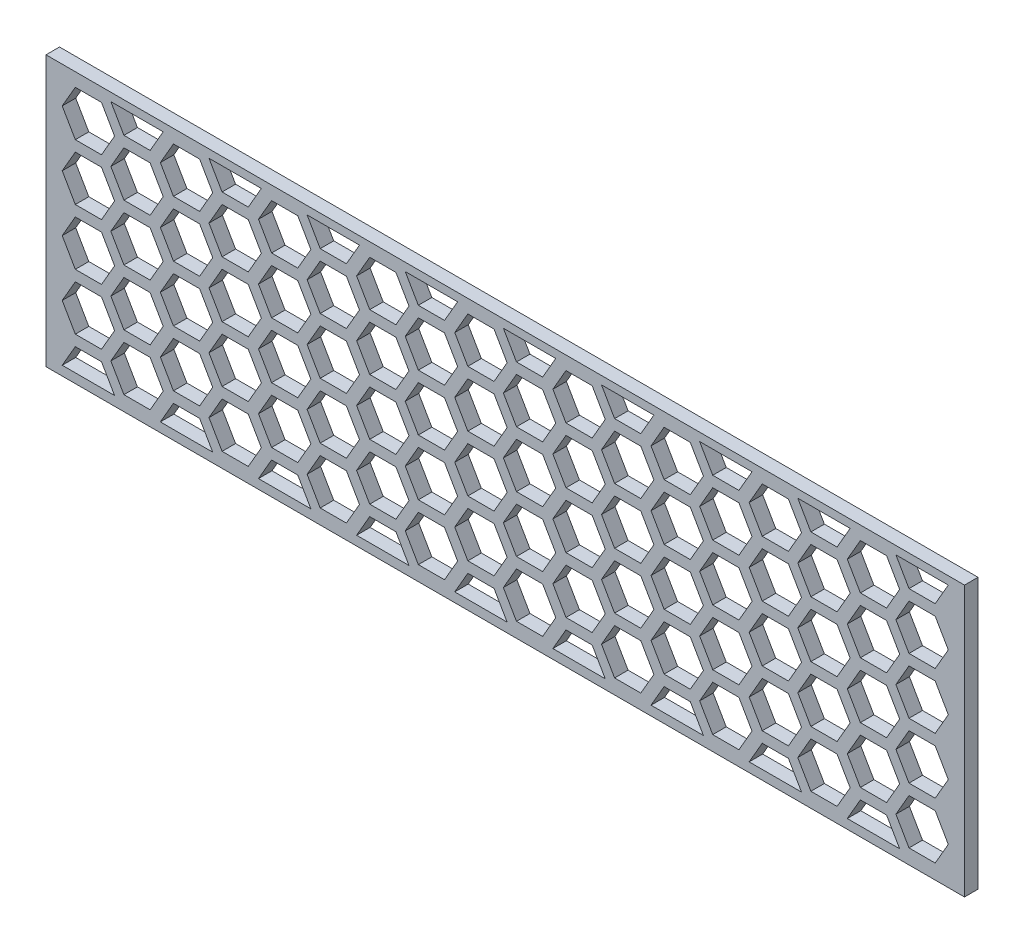
SolidWorks part; units mm, degrees
ref_plane "Plano frontal" through (0, 0, 0) normal (0, 0, 1) x (1, 0, 0)
ref_plane "Plano superior" through (0, 0, 0) normal (0, 1, 0) x (1, 0, 0)
ref_plane "Plano direito" through (0, 0, 0) normal (1, 0, 0) x (0, 0, -1)
sketch "Esboço1" plane through (0, 0, 0) normal (0, 0, 1) x (1, 0, 0)
  line L1 (-85, 25) -> (85, 25)
  line L2 (-85, 25) -> (-85, -25)
  line L3 (-85, -25) -> (85, -25)
  line L4 (85, 25) -> (85, -25)
  line L5 (-85, 25) -> (85, -25) construction
  line L6 (-85, -25) -> (85, 25) construction
  point P0 (0, 0)
  dimension "D1" = 170
  dimension "D2" = 50
extrude "Ressalto-extrusão1" add sketch "Esboço1" along normal blind 2.5
sketch "Esboço3" plane through (0, 0, 0) normal (0, 0, -1) x (-1, 0, 0)
  line L0 (-72.3051, 23.5) -> (-70.5763, 22.5019) construction
  line L4 (-82, 23.5) -> (-79.5763, 19.302)
  line L5 (-79.5763, 19.302) -> (-74.7288, 19.302)
  line L6 (-74.7288, 19.302) -> (-72.3051, 23.5)
  line L7 (-63.3051, 18.3038) -> (-65.7288, 22.5019)
  line L8 (-65.7288, 22.5019) -> (-70.5763, 22.5019)
  line L9 (-70.5763, 22.5019) -> (-73, 18.3038)
  line L10 (-73, 18.3038) -> (-70.5763, 14.1058)
  line L11 (-70.5763, 14.1058) -> (-65.7288, 14.1058)
  line L12 (-65.7288, 14.1058) -> (-63.3051, 18.3038)
  line L13 (-85, 25) -> (85, 25) construction
  line L14 (63.3051, 23.5) -> (73, 23.5)
  line L15 (-73, 18.3038) -> (-80.4849, 18.3038) construction
  line L19 (-63.8369, 23.5) -> (-61.4131, 19.302)
  line L20 (-61.4131, 19.302) -> (-56.5657, 19.302)
  line L21 (-56.5657, 19.302) -> (-54.142, 23.5)
  line L22 (-45.142, 18.3038) -> (-47.5657, 22.5019)
  line L23 (-47.5657, 22.5019) -> (-52.4131, 22.5019)
  line L24 (-52.4131, 22.5019) -> (-54.8369, 18.3038)
  line L25 (-54.8369, 18.3038) -> (-52.4131, 14.1058)
  line L26 (-52.4131, 14.1058) -> (-47.5657, 14.1058)
  line L27 (-47.5657, 14.1058) -> (-45.142, 18.3038)
  line L31 (-45.6737, 23.5) -> (-43.25, 19.302)
  line L32 (-43.25, 19.302) -> (-38.4026, 19.302)
  line L33 (-38.4026, 19.302) -> (-35.9788, 23.5)
  line L34 (-26.9788, 18.3038) -> (-29.4026, 22.5019)
  line L35 (-29.4026, 22.5019) -> (-34.25, 22.5019)
  line L36 (-34.25, 22.5019) -> (-36.6737, 18.3038)
  line L37 (-36.6737, 18.3038) -> (-34.25, 14.1058)
  line L38 (-34.25, 14.1058) -> (-29.4026, 14.1058)
  line L39 (-29.4026, 14.1058) -> (-26.9788, 18.3038)
  line L43 (-27.5106, 23.5) -> (-25.0869, 19.302)
  line L44 (-25.0869, 19.302) -> (-20.2394, 19.302)
  line L45 (-20.2394, 19.302) -> (-17.8157, 23.5)
  line L46 (-8.8157, 18.3038) -> (-11.2394, 22.5019)
  line L47 (-11.2394, 22.5019) -> (-16.0869, 22.5019)
  line L48 (-16.0869, 22.5019) -> (-18.5106, 18.3038)
  line L49 (-18.5106, 18.3038) -> (-16.0869, 14.1058)
  line L50 (-16.0869, 14.1058) -> (-11.2394, 14.1058)
  line L51 (-11.2394, 14.1058) -> (-8.8157, 18.3038)
  line L55 (-9.3474, 23.5) -> (-6.9237, 19.302)
  line L56 (-6.9237, 19.302) -> (-2.0763, 19.302)
  line L57 (-2.0763, 19.302) -> (0.3474, 23.5)
  line L58 (9.3474, 18.3038) -> (6.9237, 22.5019)
  line L59 (6.9237, 22.5019) -> (2.0763, 22.5019)
  line L60 (2.0763, 22.5019) -> (-0.3474, 18.3038)
  line L61 (-0.3474, 18.3038) -> (2.0763, 14.1058)
  line L62 (2.0763, 14.1058) -> (6.9237, 14.1058)
  line L63 (6.9237, 14.1058) -> (9.3474, 18.3038)
  line L67 (8.8157, 23.5) -> (11.2394, 19.302)
  line L68 (11.2394, 19.302) -> (16.0869, 19.302)
  line L69 (16.0869, 19.302) -> (18.5106, 23.5)
  line L70 (27.5106, 18.3038) -> (25.0869, 22.5019)
  line L71 (25.0869, 22.5019) -> (20.2394, 22.5019)
  line L72 (20.2394, 22.5019) -> (17.8157, 18.3038)
  line L73 (17.8157, 18.3038) -> (20.2394, 14.1058)
  line L74 (20.2394, 14.1058) -> (25.0869, 14.1058)
  line L75 (25.0869, 14.1058) -> (27.5106, 18.3038)
  line L79 (26.9788, 23.5) -> (29.4026, 19.302)
  line L80 (29.4026, 19.302) -> (34.25, 19.302)
  line L81 (34.25, 19.302) -> (36.6737, 23.5)
  line L82 (45.6737, 18.3038) -> (43.25, 22.5019)
  line L83 (43.25, 22.5019) -> (38.4026, 22.5019)
  line L84 (38.4026, 22.5019) -> (35.9788, 18.3038)
  line L85 (35.9788, 18.3038) -> (38.4026, 14.1058)
  line L86 (38.4026, 14.1058) -> (43.25, 14.1058)
  line L87 (43.25, 14.1058) -> (45.6737, 18.3038)
  line L91 (45.142, 23.5) -> (47.5657, 19.302)
  line L92 (47.5657, 19.302) -> (52.4131, 19.302)
  line L93 (52.4131, 19.302) -> (54.8369, 23.5)
  line L94 (63.8369, 18.3038) -> (61.4131, 22.5019)
  line L95 (61.4131, 22.5019) -> (56.5657, 22.5019)
  line L96 (56.5657, 22.5019) -> (54.142, 18.3038)
  line L97 (54.142, 18.3038) -> (56.5657, 14.1058)
  line L98 (56.5657, 14.1058) -> (61.4131, 14.1058)
  line L99 (61.4131, 14.1058) -> (63.8369, 18.3038)
  line L103 (63.3051, 23.5) -> (65.7288, 19.302)
  line L104 (65.7288, 19.302) -> (70.5763, 19.302)
  line L105 (70.5763, 19.302) -> (73, 23.5)
  line L106 (82, 18.3038) -> (79.5763, 22.5019)
  line L107 (79.5763, 22.5019) -> (74.7288, 22.5019)
  line L108 (74.7288, 22.5019) -> (72.3051, 18.3038)
  line L109 (72.3051, 18.3038) -> (74.7288, 14.1058)
  line L110 (74.7288, 14.1058) -> (79.5763, 14.1058)
  line L111 (79.5763, 14.1058) -> (82, 18.3038)
  line L112 (-54.142, 13.1077) -> (-56.5657, 17.3057)
  line L113 (-56.5657, 17.3057) -> (-61.4131, 17.3057)
  line L114 (-61.4131, 17.3057) -> (-63.8369, 13.1077)
  line L115 (-63.8369, 13.1077) -> (-61.4131, 8.9097)
  line L116 (-61.4131, 8.9097) -> (-56.5657, 8.9097)
  line L117 (-56.5657, 8.9097) -> (-54.142, 13.1077)
  line L118 (-45.142, 7.9115) -> (-47.5657, 12.1095)
  line L119 (-47.5657, 12.1095) -> (-52.4131, 12.1095)
  line L120 (-52.4131, 12.1095) -> (-54.8369, 7.9115)
  line L121 (-54.8369, 7.9115) -> (-52.4131, 3.7135)
  line L122 (-52.4131, 3.7135) -> (-47.5657, 3.7135)
  line L123 (-47.5657, 3.7135) -> (-45.142, 7.9115)
  line L124 (-35.9788, 13.1077) -> (-38.4026, 17.3057)
  line L125 (-38.4026, 17.3057) -> (-43.25, 17.3057)
  line L126 (-43.25, 17.3057) -> (-45.6737, 13.1077)
  line L127 (-45.6737, 13.1077) -> (-43.25, 8.9097)
  line L128 (-43.25, 8.9097) -> (-38.4026, 8.9097)
  line L129 (-38.4026, 8.9097) -> (-35.9788, 13.1077)
  line L130 (-26.9788, 7.9115) -> (-29.4026, 12.1095)
  line L131 (-29.4026, 12.1095) -> (-34.25, 12.1095)
  line L132 (-34.25, 12.1095) -> (-36.6737, 7.9115)
  line L133 (-36.6737, 7.9115) -> (-34.25, 3.7135)
  line L134 (-34.25, 3.7135) -> (-29.4026, 3.7135)
  line L135 (-29.4026, 3.7135) -> (-26.9788, 7.9115)
  line L136 (-17.8157, 13.1077) -> (-20.2394, 17.3057)
  line L137 (-20.2394, 17.3057) -> (-25.0869, 17.3057)
  line L138 (-25.0869, 17.3057) -> (-27.5106, 13.1077)
  line L139 (-27.5106, 13.1077) -> (-25.0869, 8.9097)
  line L140 (-25.0869, 8.9097) -> (-20.2394, 8.9097)
  line L141 (-20.2394, 8.9097) -> (-17.8157, 13.1077)
  line L142 (-8.8157, 7.9115) -> (-11.2394, 12.1095)
  line L143 (-11.2394, 12.1095) -> (-16.0869, 12.1095)
  line L144 (-16.0869, 12.1095) -> (-18.5106, 7.9115)
  line L145 (-18.5106, 7.9115) -> (-16.0869, 3.7135)
  line L146 (-16.0869, 3.7135) -> (-11.2394, 3.7135)
  line L147 (-11.2394, 3.7135) -> (-8.8157, 7.9115)
  line L148 (0.3474, 13.1077) -> (-2.0763, 17.3057)
  line L149 (-2.0763, 17.3057) -> (-6.9237, 17.3057)
  line L150 (-6.9237, 17.3057) -> (-9.3474, 13.1077)
  line L151 (-9.3474, 13.1077) -> (-6.9237, 8.9097)
  line L152 (-6.9237, 8.9097) -> (-2.0763, 8.9097)
  line L153 (-2.0763, 8.9097) -> (0.3474, 13.1077)
  line L154 (9.3474, 7.9115) -> (6.9237, 12.1095)
  line L155 (6.9237, 12.1095) -> (2.0763, 12.1095)
  line L156 (2.0763, 12.1095) -> (-0.3474, 7.9115)
  line L157 (-0.3474, 7.9115) -> (2.0763, 3.7135)
  line L158 (2.0763, 3.7135) -> (6.9237, 3.7135)
  line L159 (6.9237, 3.7135) -> (9.3474, 7.9115)
  line L160 (18.5106, 13.1077) -> (16.0869, 17.3057)
  line L161 (16.0869, 17.3057) -> (11.2394, 17.3057)
  line L162 (11.2394, 17.3057) -> (8.8157, 13.1077)
  line L163 (8.8157, 13.1077) -> (11.2394, 8.9097)
  line L164 (11.2394, 8.9097) -> (16.0869, 8.9097)
  line L165 (16.0869, 8.9097) -> (18.5106, 13.1077)
  line L166 (27.5106, 7.9115) -> (25.0869, 12.1095)
  line L167 (25.0869, 12.1095) -> (20.2394, 12.1095)
  line L168 (20.2394, 12.1095) -> (17.8157, 7.9115)
  line L169 (17.8157, 7.9115) -> (20.2394, 3.7135)
  line L170 (20.2394, 3.7135) -> (25.0869, 3.7135)
  line L171 (25.0869, 3.7135) -> (27.5106, 7.9115)
  line L172 (36.6737, 13.1077) -> (34.25, 17.3057)
  line L173 (34.25, 17.3057) -> (29.4026, 17.3057)
  line L174 (29.4026, 17.3057) -> (26.9788, 13.1077)
  line L175 (26.9788, 13.1077) -> (29.4026, 8.9097)
  line L176 (29.4026, 8.9097) -> (34.25, 8.9097)
  line L177 (34.25, 8.9097) -> (36.6737, 13.1077)
  line L178 (45.6737, 7.9115) -> (43.25, 12.1095)
  line L179 (43.25, 12.1095) -> (38.4026, 12.1095)
  line L180 (38.4026, 12.1095) -> (35.9788, 7.9115)
  line L181 (35.9788, 7.9115) -> (38.4026, 3.7135)
  line L182 (38.4026, 3.7135) -> (43.25, 3.7135)
  line L183 (43.25, 3.7135) -> (45.6737, 7.9115)
  line L184 (54.8369, 13.1077) -> (52.4131, 17.3057)
  line L185 (52.4131, 17.3057) -> (47.5657, 17.3057)
  line L186 (47.5657, 17.3057) -> (45.142, 13.1077)
  line L187 (45.142, 13.1077) -> (47.5657, 8.9097)
  line L188 (47.5657, 8.9097) -> (52.4131, 8.9097)
  line L189 (52.4131, 8.9097) -> (54.8369, 13.1077)
  line L190 (63.8369, 7.9115) -> (61.4131, 12.1095)
  line L191 (61.4131, 12.1095) -> (56.5657, 12.1095)
  line L192 (56.5657, 12.1095) -> (54.142, 7.9115)
  line L193 (54.142, 7.9115) -> (56.5657, 3.7135)
  line L194 (56.5657, 3.7135) -> (61.4131, 3.7135)
  line L195 (61.4131, 3.7135) -> (63.8369, 7.9115)
  line L196 (73, 13.1077) -> (70.5763, 17.3057)
  line L197 (70.5763, 17.3057) -> (65.7288, 17.3057)
  line L198 (65.7288, 17.3057) -> (63.3051, 13.1077)
  line L199 (63.3051, 13.1077) -> (65.7288, 8.9097)
  line L200 (65.7288, 8.9097) -> (70.5763, 8.9097)
  line L201 (70.5763, 8.9097) -> (73, 13.1077)
  line L202 (82, 7.9115) -> (79.5763, 12.1095)
  line L203 (79.5763, 12.1095) -> (74.7288, 12.1095)
  line L204 (74.7288, 12.1095) -> (72.3051, 7.9115)
  line L205 (72.3051, 7.9115) -> (74.7288, 3.7135)
  line L206 (74.7288, 3.7135) -> (79.5763, 3.7135)
  line L207 (79.5763, 3.7135) -> (82, 7.9115)
  line L208 (-54.142, 2.7154) -> (-56.5657, 6.9134)
  line L209 (-56.5657, 6.9134) -> (-61.4131, 6.9134)
  line L210 (-61.4131, 6.9134) -> (-63.8369, 2.7154)
  line L211 (-63.8369, 2.7154) -> (-61.4131, -1.4826)
  line L212 (-61.4131, -1.4826) -> (-56.5657, -1.4826)
  line L213 (-56.5657, -1.4826) -> (-54.142, 2.7154)
  line L214 (-45.142, -2.4808) -> (-47.5657, 1.7172)
  line L215 (-47.5657, 1.7172) -> (-52.4131, 1.7172)
  line L216 (-52.4131, 1.7172) -> (-54.8369, -2.4808)
  line L217 (-54.8369, -2.4808) -> (-52.4131, -6.6788)
  line L218 (-52.4131, -6.6788) -> (-47.5657, -6.6788)
  line L219 (-47.5657, -6.6788) -> (-45.142, -2.4808)
  line L220 (-35.9788, 2.7154) -> (-38.4026, 6.9134)
  line L221 (-38.4026, 6.9134) -> (-43.25, 6.9134)
  line L222 (-43.25, 6.9134) -> (-45.6737, 2.7154)
  line L223 (-45.6737, 2.7154) -> (-43.25, -1.4826)
  line L224 (-43.25, -1.4826) -> (-38.4026, -1.4826)
  line L225 (-38.4026, -1.4826) -> (-35.9788, 2.7154)
  line L226 (-26.9788, -2.4808) -> (-29.4026, 1.7172)
  line L227 (-29.4026, 1.7172) -> (-34.25, 1.7172)
  line L228 (-34.25, 1.7172) -> (-36.6737, -2.4808)
  line L229 (-36.6737, -2.4808) -> (-34.25, -6.6788)
  line L230 (-34.25, -6.6788) -> (-29.4026, -6.6788)
  line L231 (-29.4026, -6.6788) -> (-26.9788, -2.4808)
  line L232 (-17.8157, 2.7154) -> (-20.2394, 6.9134)
  line L233 (-20.2394, 6.9134) -> (-25.0869, 6.9134)
  line L234 (-25.0869, 6.9134) -> (-27.5106, 2.7154)
  line L235 (-27.5106, 2.7154) -> (-25.0869, -1.4826)
  line L236 (-25.0869, -1.4826) -> (-20.2394, -1.4826)
  line L237 (-20.2394, -1.4826) -> (-17.8157, 2.7154)
  line L238 (-8.8157, -2.4808) -> (-11.2394, 1.7172)
  line L239 (-11.2394, 1.7172) -> (-16.0869, 1.7172)
  line L240 (-16.0869, 1.7172) -> (-18.5106, -2.4808)
  line L241 (-18.5106, -2.4808) -> (-16.0869, -6.6788)
  line L242 (-16.0869, -6.6788) -> (-11.2394, -6.6788)
  line L243 (-11.2394, -6.6788) -> (-8.8157, -2.4808)
  line L244 (0.3474, 2.7154) -> (-2.0763, 6.9134)
  line L245 (-2.0763, 6.9134) -> (-6.9237, 6.9134)
  line L246 (-6.9237, 6.9134) -> (-9.3474, 2.7154)
  line L247 (-9.3474, 2.7154) -> (-6.9237, -1.4826)
  line L248 (-6.9237, -1.4826) -> (-2.0763, -1.4826)
  line L249 (-2.0763, -1.4826) -> (0.3474, 2.7154)
  line L250 (9.3474, -2.4808) -> (6.9237, 1.7172)
  line L251 (6.9237, 1.7172) -> (2.0763, 1.7172)
  line L252 (2.0763, 1.7172) -> (-0.3474, -2.4808)
  line L253 (-0.3474, -2.4808) -> (2.0763, -6.6788)
  line L254 (2.0763, -6.6788) -> (6.9237, -6.6788)
  line L255 (6.9237, -6.6788) -> (9.3474, -2.4808)
  line L256 (18.5106, 2.7154) -> (16.0869, 6.9134)
  line L257 (16.0869, 6.9134) -> (11.2394, 6.9134)
  line L258 (11.2394, 6.9134) -> (8.8157, 2.7154)
  line L259 (8.8157, 2.7154) -> (11.2394, -1.4826)
  line L260 (11.2394, -1.4826) -> (16.0869, -1.4826)
  line L261 (16.0869, -1.4826) -> (18.5106, 2.7154)
  line L262 (27.5106, -2.4808) -> (25.0869, 1.7172)
  line L263 (25.0869, 1.7172) -> (20.2394, 1.7172)
  line L264 (20.2394, 1.7172) -> (17.8157, -2.4808)
  line L265 (17.8157, -2.4808) -> (20.2394, -6.6788)
  line L266 (20.2394, -6.6788) -> (25.0869, -6.6788)
  line L267 (25.0869, -6.6788) -> (27.5106, -2.4808)
  line L268 (36.6737, 2.7154) -> (34.25, 6.9134)
  line L269 (34.25, 6.9134) -> (29.4026, 6.9134)
  line L270 (29.4026, 6.9134) -> (26.9788, 2.7154)
  line L271 (26.9788, 2.7154) -> (29.4026, -1.4826)
  line L272 (29.4026, -1.4826) -> (34.25, -1.4826)
  line L273 (34.25, -1.4826) -> (36.6737, 2.7154)
  line L274 (45.6737, -2.4808) -> (43.25, 1.7172)
  line L275 (43.25, 1.7172) -> (38.4026, 1.7172)
  line L276 (38.4026, 1.7172) -> (35.9788, -2.4808)
  line L277 (35.9788, -2.4808) -> (38.4026, -6.6788)
  line L278 (38.4026, -6.6788) -> (43.25, -6.6788)
  line L279 (43.25, -6.6788) -> (45.6737, -2.4808)
  line L280 (54.8369, 2.7154) -> (52.4131, 6.9134)
  line L281 (52.4131, 6.9134) -> (47.5657, 6.9134)
  line L282 (47.5657, 6.9134) -> (45.142, 2.7154)
  line L283 (45.142, 2.7154) -> (47.5657, -1.4826)
  line L284 (47.5657, -1.4826) -> (52.4131, -1.4826)
  line L285 (52.4131, -1.4826) -> (54.8369, 2.7154)
  line L286 (63.8369, -2.4808) -> (61.4131, 1.7172)
  line L287 (61.4131, 1.7172) -> (56.5657, 1.7172)
  line L288 (56.5657, 1.7172) -> (54.142, -2.4808)
  line L289 (54.142, -2.4808) -> (56.5657, -6.6788)
  line L290 (56.5657, -6.6788) -> (61.4131, -6.6788)
  line L291 (61.4131, -6.6788) -> (63.8369, -2.4808)
  line L292 (73, 2.7154) -> (70.5763, 6.9134)
  line L293 (70.5763, 6.9134) -> (65.7288, 6.9134)
  line L294 (65.7288, 6.9134) -> (63.3051, 2.7154)
  line L295 (63.3051, 2.7154) -> (65.7288, -1.4826)
  line L296 (65.7288, -1.4826) -> (70.5763, -1.4826)
  line L297 (70.5763, -1.4826) -> (73, 2.7154)
  line L298 (82, -2.4808) -> (79.5763, 1.7172)
  line L299 (79.5763, 1.7172) -> (74.7288, 1.7172)
  line L300 (74.7288, 1.7172) -> (72.3051, -2.4808)
  line L301 (72.3051, -2.4808) -> (74.7288, -6.6788)
  line L302 (74.7288, -6.6788) -> (79.5763, -6.6788)
  line L303 (79.5763, -6.6788) -> (82, -2.4808)
  line L304 (-54.142, -7.6769) -> (-56.5657, -3.4789)
  line L305 (-56.5657, -3.4789) -> (-61.4131, -3.4789)
  line L306 (-61.4131, -3.4789) -> (-63.8369, -7.6769)
  line L307 (-63.8369, -7.6769) -> (-61.4131, -11.8749)
  line L308 (-61.4131, -11.8749) -> (-56.5657, -11.8749)
  line L309 (-56.5657, -11.8749) -> (-54.142, -7.6769)
  line L310 (-45.142, -12.8731) -> (-47.5657, -8.6751)
  line L311 (-47.5657, -8.6751) -> (-52.4131, -8.6751)
  line L312 (-52.4131, -8.6751) -> (-54.8369, -12.8731)
  line L313 (-54.8369, -12.8731) -> (-52.4131, -17.0711)
  line L314 (-52.4131, -17.0711) -> (-47.5657, -17.0711)
  line L315 (-47.5657, -17.0711) -> (-45.142, -12.8731)
  line L316 (-35.9788, -7.6769) -> (-38.4026, -3.4789)
  line L317 (-38.4026, -3.4789) -> (-43.25, -3.4789)
  line L318 (-43.25, -3.4789) -> (-45.6737, -7.6769)
  line L319 (-45.6737, -7.6769) -> (-43.25, -11.8749)
  line L320 (-43.25, -11.8749) -> (-38.4026, -11.8749)
  line L321 (-38.4026, -11.8749) -> (-35.9788, -7.6769)
  line L322 (-26.9788, -12.8731) -> (-29.4026, -8.6751)
  line L323 (-29.4026, -8.6751) -> (-34.25, -8.6751)
  line L324 (-34.25, -8.6751) -> (-36.6737, -12.8731)
  line L325 (-36.6737, -12.8731) -> (-34.25, -17.0711)
  line L326 (-34.25, -17.0711) -> (-29.4026, -17.0711)
  line L327 (-29.4026, -17.0711) -> (-26.9788, -12.8731)
  line L328 (-17.8157, -7.6769) -> (-20.2394, -3.4789)
  line L329 (-20.2394, -3.4789) -> (-25.0869, -3.4789)
  line L330 (-25.0869, -3.4789) -> (-27.5106, -7.6769)
  line L331 (-27.5106, -7.6769) -> (-25.0869, -11.8749)
  line L332 (-25.0869, -11.8749) -> (-20.2394, -11.8749)
  line L333 (-20.2394, -11.8749) -> (-17.8157, -7.6769)
  line L334 (-8.8157, -12.8731) -> (-11.2394, -8.6751)
  line L335 (-11.2394, -8.6751) -> (-16.0869, -8.6751)
  line L336 (-16.0869, -8.6751) -> (-18.5106, -12.8731)
  line L337 (-18.5106, -12.8731) -> (-16.0869, -17.0711)
  line L338 (-16.0869, -17.0711) -> (-11.2394, -17.0711)
  line L339 (-11.2394, -17.0711) -> (-8.8157, -12.8731)
  line L340 (0.3474, -7.6769) -> (-2.0763, -3.4789)
  line L341 (-2.0763, -3.4789) -> (-6.9237, -3.4789)
  line L342 (-6.9237, -3.4789) -> (-9.3474, -7.6769)
  line L343 (-9.3474, -7.6769) -> (-6.9237, -11.8749)
  line L344 (-6.9237, -11.8749) -> (-2.0763, -11.8749)
  line L345 (-2.0763, -11.8749) -> (0.3474, -7.6769)
  line L346 (9.3474, -12.8731) -> (6.9237, -8.6751)
  line L347 (6.9237, -8.6751) -> (2.0763, -8.6751)
  line L348 (2.0763, -8.6751) -> (-0.3474, -12.8731)
  line L349 (-0.3474, -12.8731) -> (2.0763, -17.0711)
  line L350 (2.0763, -17.0711) -> (6.9237, -17.0711)
  line L351 (6.9237, -17.0711) -> (9.3474, -12.8731)
  line L352 (18.5106, -7.6769) -> (16.0869, -3.4789)
  line L353 (16.0869, -3.4789) -> (11.2394, -3.4789)
  line L354 (11.2394, -3.4789) -> (8.8157, -7.6769)
  line L355 (8.8157, -7.6769) -> (11.2394, -11.8749)
  line L356 (11.2394, -11.8749) -> (16.0869, -11.8749)
  line L357 (16.0869, -11.8749) -> (18.5106, -7.6769)
  line L358 (27.5106, -12.8731) -> (25.0869, -8.6751)
  line L359 (25.0869, -8.6751) -> (20.2394, -8.6751)
  line L360 (20.2394, -8.6751) -> (17.8157, -12.8731)
  line L361 (17.8157, -12.8731) -> (20.2394, -17.0711)
  line L362 (20.2394, -17.0711) -> (25.0869, -17.0711)
  line L363 (25.0869, -17.0711) -> (27.5106, -12.8731)
  line L364 (36.6737, -7.6769) -> (34.25, -3.4789)
  line L365 (34.25, -3.4789) -> (29.4026, -3.4789)
  line L366 (29.4026, -3.4789) -> (26.9788, -7.6769)
  line L367 (26.9788, -7.6769) -> (29.4026, -11.8749)
  line L368 (29.4026, -11.8749) -> (34.25, -11.8749)
  line L369 (34.25, -11.8749) -> (36.6737, -7.6769)
  line L370 (45.6737, -12.8731) -> (43.25, -8.6751)
  line L371 (43.25, -8.6751) -> (38.4026, -8.6751)
  line L372 (38.4026, -8.6751) -> (35.9788, -12.8731)
  line L373 (35.9788, -12.8731) -> (38.4026, -17.0711)
  line L374 (38.4026, -17.0711) -> (43.25, -17.0711)
  line L375 (43.25, -17.0711) -> (45.6737, -12.8731)
  line L376 (54.8369, -7.6769) -> (52.4131, -3.4789)
  line L377 (52.4131, -3.4789) -> (47.5657, -3.4789)
  line L378 (47.5657, -3.4789) -> (45.142, -7.6769)
  line L379 (45.142, -7.6769) -> (47.5657, -11.8749)
  line L380 (47.5657, -11.8749) -> (52.4131, -11.8749)
  line L381 (52.4131, -11.8749) -> (54.8369, -7.6769)
  line L382 (63.8369, -12.8731) -> (61.4131, -8.6751)
  line L383 (61.4131, -8.6751) -> (56.5657, -8.6751)
  line L384 (56.5657, -8.6751) -> (54.142, -12.8731)
  line L385 (54.142, -12.8731) -> (56.5657, -17.0711)
  line L386 (56.5657, -17.0711) -> (61.4131, -17.0711)
  line L387 (61.4131, -17.0711) -> (63.8369, -12.8731)
  line L388 (73, -7.6769) -> (70.5763, -3.4789)
  line L389 (70.5763, -3.4789) -> (65.7288, -3.4789)
  line L390 (65.7288, -3.4789) -> (63.3051, -7.6769)
  line L391 (63.3051, -7.6769) -> (65.7288, -11.8749)
  line L392 (65.7288, -11.8749) -> (70.5763, -11.8749)
  line L393 (70.5763, -11.8749) -> (73, -7.6769)
  line L394 (82, -12.8731) -> (79.5763, -8.6751)
  line L395 (79.5763, -8.6751) -> (74.7288, -8.6751)
  line L396 (74.7288, -8.6751) -> (72.3051, -12.8731)
  line L397 (72.3051, -12.8731) -> (74.7288, -17.0711)
  line L398 (74.7288, -17.0711) -> (79.5763, -17.0711)
  line L399 (79.5763, -17.0711) -> (82, -12.8731)
  line L400 (-72.3051, 13.1077) -> (-74.7288, 17.3057)
  line L401 (-74.7288, 17.3057) -> (-79.5763, 17.3057)
  line L402 (-79.5763, 17.3057) -> (-82, 13.1077)
  line L403 (-82, 13.1077) -> (-79.5763, 8.9097)
  line L404 (-79.5763, 8.9097) -> (-74.7288, 8.9097)
  line L405 (-74.7288, 8.9097) -> (-72.3051, 13.1077)
  line L406 (-63.3051, 7.9115) -> (-65.7288, 12.1095)
  line L407 (-65.7288, 12.1095) -> (-70.5763, 12.1095)
  line L408 (-70.5763, 12.1095) -> (-73, 7.9115)
  line L409 (-73, 7.9115) -> (-70.5763, 3.7135)
  line L410 (-70.5763, 3.7135) -> (-65.7288, 3.7135)
  line L411 (-65.7288, 3.7135) -> (-63.3051, 7.9115)
  line L412 (-72.3051, 2.7154) -> (-74.7288, 6.9134)
  line L413 (-74.7288, 6.9134) -> (-79.5763, 6.9134)
  line L414 (-79.5763, 6.9134) -> (-82, 2.7154)
  line L415 (-82, 2.7154) -> (-79.5763, -1.4826)
  line L416 (-79.5763, -1.4826) -> (-74.7288, -1.4826)
  line L417 (-74.7288, -1.4826) -> (-72.3051, 2.7154)
  line L418 (-63.3051, -2.4808) -> (-65.7288, 1.7172)
  line L419 (-65.7288, 1.7172) -> (-70.5763, 1.7172)
  line L420 (-70.5763, 1.7172) -> (-73, -2.4808)
  line L421 (-73, -2.4808) -> (-70.5763, -6.6788)
  line L422 (-70.5763, -6.6788) -> (-65.7288, -6.6788)
  line L423 (-65.7288, -6.6788) -> (-63.3051, -2.4808)
  line L424 (-72.3051, -7.6769) -> (-74.7288, -3.4789)
  line L425 (-74.7288, -3.4789) -> (-79.5763, -3.4789)
  line L426 (-79.5763, -3.4789) -> (-82, -7.6769)
  line L427 (-82, -7.6769) -> (-79.5763, -11.8749)
  line L428 (-79.5763, -11.8749) -> (-74.7288, -11.8749)
  line L429 (-74.7288, -11.8749) -> (-72.3051, -7.6769)
  line L430 (-63.3051, -12.8731) -> (-65.7288, -8.6751)
  line L431 (-65.7288, -8.6751) -> (-70.5763, -8.6751)
  line L432 (-70.5763, -8.6751) -> (-73, -12.8731)
  line L433 (-73, -12.8731) -> (-70.5763, -17.0711)
  line L434 (-70.5763, -17.0711) -> (-65.7288, -17.0711)
  line L435 (-65.7288, -17.0711) -> (-63.3051, -12.8731)
  line L436 (-72.3051, -18.0692) -> (-74.7288, -13.8712)
  line L437 (-74.7288, -13.8712) -> (-79.5763, -13.8712)
  line L438 (-79.5763, -13.8712) -> (-82, -18.0692)
  line L439 (-82, -18.0692) -> (-79.5763, -22.2672)
  line L440 (-79.5763, -22.2672) -> (-74.7288, -22.2672)
  line L441 (-74.7288, -22.2672) -> (-72.3051, -18.0692)
  line L442 (-63.3051, -23.2654) -> (-65.7288, -19.0674)
  line L443 (-65.7288, -19.0674) -> (-70.5763, -19.0674)
  line L444 (-70.5763, -19.0674) -> (-73, -23.2654)
  line L448 (-54.142, -18.0692) -> (-56.5657, -13.8712)
  line L449 (-56.5657, -13.8712) -> (-61.4131, -13.8712)
  line L450 (-61.4131, -13.8712) -> (-63.8369, -18.0692)
  line L451 (-63.8369, -18.0692) -> (-61.4131, -22.2672)
  line L452 (-61.4131, -22.2672) -> (-56.5657, -22.2672)
  line L453 (-56.5657, -22.2672) -> (-54.142, -18.0692)
  line L454 (-45.142, -23.2654) -> (-47.5657, -19.0674)
  line L455 (-47.5657, -19.0674) -> (-52.4131, -19.0674)
  line L456 (-52.4131, -19.0674) -> (-54.8369, -23.2654)
  line L460 (-35.9788, -18.0692) -> (-38.4026, -13.8712)
  line L461 (-38.4026, -13.8712) -> (-43.25, -13.8712)
  line L462 (-43.25, -13.8712) -> (-45.6737, -18.0692)
  line L463 (-45.6737, -18.0692) -> (-43.25, -22.2672)
  line L464 (-43.25, -22.2672) -> (-38.4026, -22.2672)
  line L465 (-38.4026, -22.2672) -> (-35.9788, -18.0692)
  line L466 (-26.9788, -23.2654) -> (-29.4026, -19.0674)
  line L467 (-29.4026, -19.0674) -> (-34.25, -19.0674)
  line L468 (-34.25, -19.0674) -> (-36.6737, -23.2654)
  line L472 (-17.8157, -18.0692) -> (-20.2394, -13.8712)
  line L473 (-20.2394, -13.8712) -> (-25.0869, -13.8712)
  line L474 (-25.0869, -13.8712) -> (-27.5106, -18.0692)
  line L475 (-27.5106, -18.0692) -> (-25.0869, -22.2672)
  line L476 (-25.0869, -22.2672) -> (-20.2394, -22.2672)
  line L477 (-20.2394, -22.2672) -> (-17.8157, -18.0692)
  line L478 (-8.8157, -23.2654) -> (-11.2394, -19.0674)
  line L479 (-11.2394, -19.0674) -> (-16.0869, -19.0674)
  line L480 (-16.0869, -19.0674) -> (-18.5106, -23.2654)
  line L484 (0.3474, -18.0692) -> (-2.0763, -13.8712)
  line L485 (-2.0763, -13.8712) -> (-6.9237, -13.8712)
  line L486 (-6.9237, -13.8712) -> (-9.3474, -18.0692)
  line L487 (-9.3474, -18.0692) -> (-6.9237, -22.2672)
  line L488 (-6.9237, -22.2672) -> (-2.0763, -22.2672)
  line L489 (-2.0763, -22.2672) -> (0.3474, -18.0692)
  line L490 (9.3474, -23.2654) -> (6.9237, -19.0674)
  line L491 (6.9237, -19.0674) -> (2.0763, -19.0674)
  line L492 (2.0763, -19.0674) -> (-0.3474, -23.2654)
  line L496 (18.5106, -18.0692) -> (16.0869, -13.8712)
  line L497 (16.0869, -13.8712) -> (11.2394, -13.8712)
  line L498 (11.2394, -13.8712) -> (8.8157, -18.0692)
  line L499 (8.8157, -18.0692) -> (11.2394, -22.2672)
  line L500 (11.2394, -22.2672) -> (16.0869, -22.2672)
  line L501 (16.0869, -22.2672) -> (18.5106, -18.0692)
  line L502 (27.5106, -23.2654) -> (25.0869, -19.0674)
  line L503 (25.0869, -19.0674) -> (20.2394, -19.0674)
  line L504 (20.2394, -19.0674) -> (17.8157, -23.2654)
  line L508 (36.6737, -18.0692) -> (34.25, -13.8712)
  line L509 (34.25, -13.8712) -> (29.4026, -13.8712)
  line L510 (29.4026, -13.8712) -> (26.9788, -18.0692)
  line L511 (26.9788, -18.0692) -> (29.4026, -22.2672)
  line L512 (29.4026, -22.2672) -> (34.25, -22.2672)
  line L513 (34.25, -22.2672) -> (36.6737, -18.0692)
  line L514 (45.6737, -23.2654) -> (43.25, -19.0674)
  line L515 (43.25, -19.0674) -> (38.4026, -19.0674)
  line L516 (38.4026, -19.0674) -> (35.9788, -23.2654)
  line L520 (54.8369, -18.0692) -> (52.4131, -13.8712)
  line L521 (52.4131, -13.8712) -> (47.5657, -13.8712)
  line L522 (47.5657, -13.8712) -> (45.142, -18.0692)
  line L523 (45.142, -18.0692) -> (47.5657, -22.2672)
  line L524 (47.5657, -22.2672) -> (52.4131, -22.2672)
  line L525 (52.4131, -22.2672) -> (54.8369, -18.0692)
  line L526 (63.8369, -23.2654) -> (61.4131, -19.0674)
  line L527 (61.4131, -19.0674) -> (56.5657, -19.0674)
  line L528 (56.5657, -19.0674) -> (54.142, -23.2654)
  line L532 (73, -18.0692) -> (70.5763, -13.8712)
  line L533 (70.5763, -13.8712) -> (65.7288, -13.8712)
  line L534 (65.7288, -13.8712) -> (63.3051, -18.0692)
  line L535 (63.3051, -18.0692) -> (65.7288, -22.2672)
  line L536 (65.7288, -22.2672) -> (70.5763, -22.2672)
  line L537 (70.5763, -22.2672) -> (73, -18.0692)
  line L538 (82, -23.2654) -> (79.5763, -19.0674)
  line L539 (79.5763, -19.0674) -> (74.7288, -19.0674)
  line L540 (74.7288, -19.0674) -> (72.3051, -23.2654)
  line L544 (-82, 23.5) -> (-72.3051, 23.5)
  line L545 (-73, -23.2654) -> (-63.3051, -23.2654)
  line L546 (-82, 23.5) -> (-85, 23.5) construction
  line L547 (45.142, 23.5) -> (54.8369, 23.5)
  line L548 (26.9788, 23.5) -> (36.6737, 23.5)
  line L549 (8.8157, 23.5) -> (18.5106, 23.5)
  line L550 (-9.3474, 23.5) -> (0.3474, 23.5)
  line L551 (-27.5106, 23.5) -> (-17.8157, 23.5)
  line L552 (82, 18.3038) -> (85, 18.3038) construction
  line L553 (85, 25) -> (85, -25) construction
  line L554 (69.6025, -23.2654) -> (69.6025, -25) construction
  line L555 (-63.8369, 23.5) -> (-54.142, 23.5)
  line L556 (-45.6737, 23.5) -> (-35.9788, 23.5)
  line L557 (-85, -25) -> (-85, 25) construction
  line L558 (-54.8369, -23.2654) -> (-45.142, -23.2654)
  line L559 (-36.6737, -23.2654) -> (-26.9788, -23.2654)
  line L560 (85, -25) -> (-85, -25) construction
  line L561 (-74.7288, 27.698) -> (-79.5763, 27.698) [skipped]
  line L562 (-80.7881, 25.599) -> (-82, 23.5) [skipped]
  line L563 (-72.3051, 23.5) -> (-73.517, 25.599) [skipped]
  line L564 (-73, -23.2654) -> (-70.5763, -27.4634) [skipped]
  line L565 (-65.7288, -27.4634) -> (-63.3051, -23.2654) [skipped]
  line L566 (-70.5763, -27.4634) -> (-65.7288, -27.4634) [skipped]
  line L567 (-54.8369, -23.2654) -> (-52.4131, -27.4634) [skipped]
  line L568 (-52.4131, -27.4634) -> (-47.5657, -27.4634) [skipped]
  line L569 (-47.5657, -27.4634) -> (-45.142, -23.2654) [skipped]
  line L570 (-36.6737, -23.2654) -> (-34.25, -27.4634) [skipped]
  line L571 (-34.25, -27.4634) -> (-29.4026, -27.4634) [skipped]
  line L572 (-29.4026, -27.4634) -> (-26.9788, -23.2654) [skipped]
  line L573 (-18.5106, -23.2654) -> (-8.8157, -23.2654)
  line L574 (-18.5106, -23.2654) -> (-16.0869, -27.4634) [skipped]
  line L575 (-16.0869, -27.4634) -> (-11.2394, -27.4634) [skipped]
  line L576 (-11.2394, -27.4634) -> (-8.8157, -23.2654) [skipped]
  line L577 (-0.3474, -23.2654) -> (9.3474, -23.2654)
  line L578 (-0.3474, -23.2654) -> (2.0763, -27.4634) [skipped]
  line L579 (6.9237, -27.4634) -> (9.3474, -23.2654) [skipped]
  line L580 (2.0763, -27.4634) -> (6.9237, -27.4634) [skipped]
  line L581 (17.8157, -23.2654) -> (20.2394, -27.4634) [skipped]
  line L582 (20.2394, -27.4634) -> (25.0869, -27.4634) [skipped]
  line L583 (25.0869, -27.4634) -> (27.5106, -23.2654) [skipped]
  line L584 (35.9788, -23.2654) -> (38.4026, -27.4634) [skipped]
  line L585 (38.4026, -27.4634) -> (43.25, -27.4634) [skipped]
  line L586 (43.25, -27.4634) -> (45.6737, -23.2654) [skipped]
  line L587 (54.142, -23.2654) -> (56.5657, -27.4634) [skipped]
  line L588 (56.5657, -27.4634) -> (61.4131, -27.4634) [skipped]
  line L589 (61.4131, -27.4634) -> (63.8369, -23.2654) [skipped]
  line L590 (72.3051, -23.2654) -> (74.7288, -27.4634) [skipped]
  line L591 (74.7288, -27.4634) -> (79.5763, -27.4634) [skipped]
  line L592 (79.5763, -27.4634) -> (82, -23.2654) [skipped]
  line L593 (72.3051, -23.2654) -> (82, -23.2654)
  line L594 (54.142, -23.2654) -> (63.8369, -23.2654)
  line L595 (17.8157, -23.2654) -> (27.5106, -23.2654)
  line L596 (35.9788, -23.2654) -> (45.6737, -23.2654)
  arc A0 (-81.3506, 23.5) -> (-72.9546, 23.5) centre (-77.1526, 23.5) ccw construction
  circle A1 centre (-68.1526, 18.3038) radius 4.198 construction
  point P1 (-81.1188, 25)
  point P8 (0, 0)
  point P23 (0, 0)
  point P24 (0, 0)
  point P553 (-85, 22.4942)
  point P556 (-68.2093, 25)
  point P557 (-65.1134, 25)
  point P558 (69.6025, -25)
  point P561 (-64.9087, 25)
  point P563 (-76.8625, 23.5)
  point P564 (-65.7829, 23.3827)
  point P565 (-81.5579, 23.3827)
  point P566 (-76.5, 23.3827)
  point P567 (-76.5, 23.3827)
  point P568 (-101.969, 31.2067)
  point P569 (-81.1188, 25)
  point P570 (-76.5, 23.3827)
  point P571 (0, 0)
  point P572 (0, 0)
  dimension "D1" = 1.5
  dimension "D2" = 9
  dimension "D3" = 3
  dimension "D7" = 9
  dimension "D8" = 5
extrude "Corte-extrusão1" cut sketch "Esboço3" against normal blind 6
